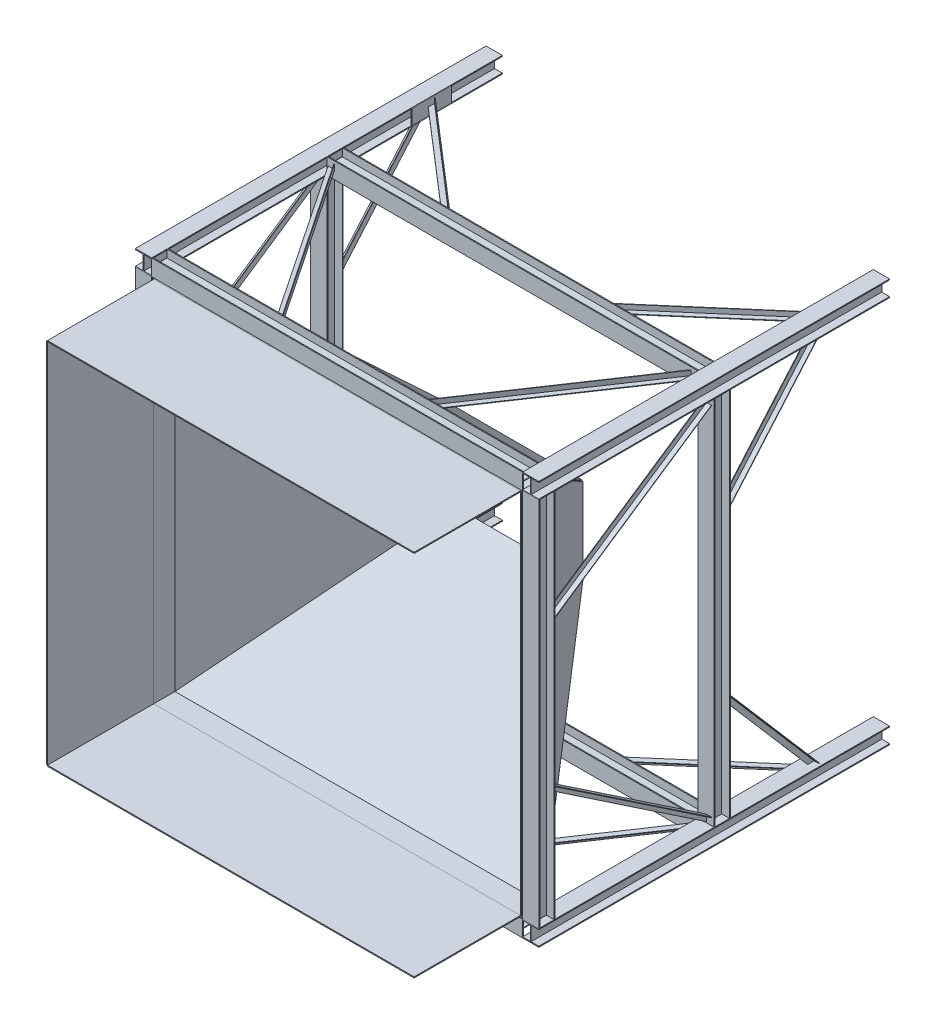
SolidWorks part; units mm, degrees
other "DetailItem1"
other "DetailItem2"
other "DetailItem3"
other "DetailItem4"
other "DetailItem5"
other "DetailItem6"
other "DetailItem7"
other "DetailItem8"
other "DetailItem9"
other "DetailItem10"
other "DetailItem11"
other "DetailItem12"
other "DetailItem13"
other "DetailItem14"
other "DetailItem15"
other "DetailItem16"
other "DetailItem17"
other "DetailItem18"
other "DetailItem19"
other "DetailItem20"
other "DetailItem21"
other "DetailItem22"
other "DetailItem23"
other "DetailItem24"
other "DetailItem25"
other "DetailItem26"
other "DetailItem27"
other "DetailItem28"
other "DetailItem29"
other "DetailItem30"
other "DetailItem31"
other "DetailItem32"
other "DetailItem33"
other "DetailItem34"
other "DetailItem35"
other "DetailItem36"
other "DetailItem37"
other "DetailItem38"
other "DetailItem39"
other "DetailItem40"
other "DetailItem41"
other "DetailItem42"
other "DetailItem43"
other "DetailItem44"
other "DetailItem45"
other "DetailItem46"
other "DetailItem47"
other "DetailItem48"
other "DetailItem49"
other "DetailItem50"
other "DetailItem51"
other "DetailItem52"
other "DetailItem53"
other "DetailItem54"
other "DetailItem55"
other "DetailItem56"
other "DetailItem57"
other "DetailItem58"
other "DetailItem59"
other "DetailItem60"
other "DetailItem61"
other "DetailItem62"
other "DetailItem63"
other "DetailItem64"
other "DetailItem65"
other "DetailItem66"
other "DetailItem67"
other "DetailItem68"
other "DetailItem69"
other "DetailItem70"
other "DetailItem71"
other "DetailItem72"
other "DetailItem73"
other "Carpeta de soldadura"
other "Cordón de soldadura1"
other "Soldadura Viga H carga 1650 B"
other "Soldadura Viga H carga 3300 A"
other "Soldadura Viga H carga 3300 B"
other "Soldadura asiento a tolva carga"
other "Soldadura asiento a bastidor carga"
other "Soldadura Viga H fondo 1650 A"
other "Soldadura Viga H fondo 1650 B"
other "Soldadura Viga H fondo 3300 A"
other "Soldadura Viga H fondo 3300 B"
other "Soldadura asiento a tolva fondo"
other "Soldadura asiento a bastidor fondo"
other "Soldadura Viga H izquierda 1650 A"
other "Soldadura Viga H izquierda 1650 B"
other "Soldadura Viga H izquierda 3300 A"
other "Soldadura Viga H izquierda 3300 B"
other "Soldadura asiento a tolva izquierda"
other "Soldadura asiento a bastidor izquierda"
other "Soldadura Viga H derecha 1650 A"
other "Soldadura Viga H derecha 1650 B"
other "Soldadura Viga H derecha 3300 A"
other "Soldadura Viga H derecha 3300 B"
other "Soldadura asiento a tolva derecha"
other "Soldadura asiento a bastidor derecha"
other "Soldadura Angular superior carga A inferior"
other "Soldadura Angular superior carga A superior"
other "Soldadura Angular inferior carga A inferior"
other "Soldadura Angular inferior carga A superior"
other "Soldadura Angular superior carga B inferior"
other "Soldadura Angular superior carga B superior"
other "Soldadura Angular inferior carga B inferior"
other "Soldadura Angular inferior carga B superior"
other "Soldadura Angular superior fondo A inferior"
other "Soldadura Angular superior fondo A superior"
other "Soldadura Angular inferior fondo A inferior"
other "Soldadura Angular inferior fondo A superior"
other "Soldadura Angular superior fondo B inferior"
other "Soldadura Angular superior fondo B superior"
other "Soldadura Angular inferior fondo B inferior"
other "Soldadura Angular inferior fondo B superior"
other "Soldadura Angular superior izquierda A inferior"
other "Soldadura Angular superior izquierda A superior"
other "Soldadura Angular inferior izquierda A inferior"
other "Soldadura Angular inferior izquierda A superior"
other "Soldadura Angular superior izquierda B inferior"
other "Soldadura Angular superior izquierda B superior"
other "Soldadura Angular inferior izquierda B inferior"
other "Soldadura Angular inferior izquierda B superior"
other "Soldadura Angular superior derecha A inferior"
other "Soldadura Angular superior derecha A superior"
other "Soldadura Angular inferior derecha A inferior"
other "Soldadura Angular inferior derecha A superior"
other "Soldadura Angular superior derecha B inferior"
other "Soldadura Angular superior derecha B superior"
other "Soldadura Angular inferior derecha B inferior"
other "Soldadura Angular inferior derecha B superior"
other "Soldadura alerón a collar lateral Y negativo"
other "Soldadura esquina del collar lateral Y negativo"
other "Soldadura quiebre del embudo lateral Y negativo"
other "Soldadura arista inclinada lateral Y negativo"
other "Soldadura esquina del collar carga"
other "Soldadura quiebre del embudo carga"
other "Soldadura arista inclinada carga"
other "Soldadura alerón a collar lateral Y positivo"
other "Soldadura esquina del collar lateral Y positivo"
other "Soldadura quiebre del embudo lateral Y positivo"
other "Soldadura arista inclinada lateral Y positivo"
other "Soldadura alerón a collar fondo X negativo"
other "Soldadura esquina del collar fondo X negativo"
other "Soldadura quiebre del embudo fondo X negativo"
other "Soldadura arista inclinada fondo X negativo"
other "Soldadura esquina alerones fondo Y positivo"
other "Soldadura esquina alerones fondo Y negativo"
material "ASTM A36 Steel"
ref_plane "Front Plane" through (0, 0, 0) normal (0, 0, 1) x (1, 0, 0)
ref_plane "Top Plane" through (0, 0, 0) normal (0, 1, 0) x (1, 0, 0)
ref_plane "Right Plane" through (0, 0, 0) normal (1, 0, 0) x (0, 0, -1)
sketch3d "Referencias 1"
  point P0 (0, 0, 0)
  point P1 (0, -190, 0)
  point P2 (200, 0, 0)
ref_plane "Plano de perfil 1 estructura" through (0, 0, 0) normal (0, 0, 1) x (1, 0, 0)
sketch "Contorno Columna H 1" plane through (0, 0, 0) normal (0, 0, 1) x (1, 0, 0)
  line L0 (-1898, -1898) -> (-1745, -1898)
  line L1 (-1745, -1898) -> (-1745, -1889)
  line L2 (-1745, -1889) -> (-1818.25, -1889)
  line L3 (-1818.25, -1889) -> (-1818.25, -1754)
  line L4 (-1818.25, -1754) -> (-1745, -1754)
  line L5 (-1745, -1754) -> (-1745, -1745)
  line L6 (-1745, -1745) -> (-1898, -1745)
  line L7 (-1898, -1745) -> (-1898, -1754)
  line L8 (-1898, -1754) -> (-1824.75, -1754)
  line L9 (-1824.75, -1754) -> (-1824.75, -1889)
  line L10 (-1824.75, -1889) -> (-1898, -1889)
  line L11 (-1898, -1889) -> (-1898, -1898)
extrude "Columna H 1" add sketch "Contorno Columna H 1" along normal blind 3300 separate body
sketch "Contorno Columna H 2" plane through (0, 0, 0) normal (0, 0, 1) x (1, 0, 0)
  line L0 (-1898, 1745) -> (-1745, 1745)
  line L1 (-1745, 1745) -> (-1745, 1754)
  line L2 (-1745, 1754) -> (-1818.25, 1754)
  line L3 (-1818.25, 1754) -> (-1818.25, 1889)
  line L4 (-1818.25, 1889) -> (-1745, 1889)
  line L5 (-1745, 1889) -> (-1745, 1898)
  line L6 (-1745, 1898) -> (-1898, 1898)
  line L7 (-1898, 1898) -> (-1898, 1889)
  line L8 (-1898, 1889) -> (-1824.75, 1889)
  line L9 (-1824.75, 1889) -> (-1824.75, 1754)
  line L10 (-1824.75, 1754) -> (-1898, 1754)
  line L11 (-1898, 1754) -> (-1898, 1745)
extrude "Columna H 2" add sketch "Contorno Columna H 2" along normal blind 3300 separate body
sketch "Contorno Columna H 3" plane through (0, 0, 0) normal (0, 0, 1) x (1, 0, 0)
  line L0 (1745, -1898) -> (1898, -1898)
  line L1 (1898, -1898) -> (1898, -1889)
  line L2 (1898, -1889) -> (1824.75, -1889)
  line L3 (1824.75, -1889) -> (1824.75, -1754)
  line L4 (1824.75, -1754) -> (1898, -1754)
  line L5 (1898, -1754) -> (1898, -1745)
  line L6 (1898, -1745) -> (1745, -1745)
  line L7 (1745, -1745) -> (1745, -1754)
  line L8 (1745, -1754) -> (1818.25, -1754)
  line L9 (1818.25, -1754) -> (1818.25, -1889)
  line L10 (1818.25, -1889) -> (1745, -1889)
  line L11 (1745, -1889) -> (1745, -1898)
extrude "Columna H 3" add sketch "Contorno Columna H 3" along normal blind 3300 separate body
sketch "Contorno Columna H 4" plane through (0, 0, 0) normal (0, 0, 1) x (1, 0, 0)
  line L0 (1745, 1745) -> (1898, 1745)
  line L1 (1898, 1745) -> (1898, 1754)
  line L2 (1898, 1754) -> (1824.75, 1754)
  line L3 (1824.75, 1754) -> (1824.75, 1889)
  line L4 (1824.75, 1889) -> (1898, 1889)
  line L5 (1898, 1889) -> (1898, 1898)
  line L6 (1898, 1898) -> (1745, 1898)
  line L7 (1745, 1898) -> (1745, 1889)
  line L8 (1745, 1889) -> (1818.25, 1889)
  line L9 (1818.25, 1889) -> (1818.25, 1754)
  line L10 (1818.25, 1754) -> (1745, 1754)
  line L11 (1745, 1754) -> (1745, 1745)
extrude "Columna H 4" add sketch "Contorno Columna H 4" along normal blind 3300 separate body
sketch3d "Referencias 2"
  point P0 (-1745, 0, 0)
  point P1 (-1745, 190, 0)
  point P2 (-1745, 0, 200)
ref_plane "Plano de perfil 2 estructura" through (-1745, 0, 0) normal (1, 0, 0) x (0, 0, -1)
sketch "Contorno Viga H carga 1650" plane through (-1745, 0, 0) normal (1, 0, 0) x (0, 0, -1)
  line L0 (-1497, -1745) -> (-1497, -1898)
  line L1 (-1497, -1898) -> (-1506, -1898)
  line L2 (-1506, -1898) -> (-1506, -1824.75)
  line L3 (-1506, -1824.75) -> (-1641, -1824.75)
  line L4 (-1641, -1824.75) -> (-1641, -1898)
  line L5 (-1641, -1898) -> (-1650, -1898)
  line L6 (-1650, -1898) -> (-1650, -1745)
  line L7 (-1650, -1745) -> (-1641, -1745)
  line L8 (-1641, -1745) -> (-1641, -1818.25)
  line L9 (-1641, -1818.25) -> (-1506, -1818.25)
  line L10 (-1506, -1818.25) -> (-1506, -1745)
  line L11 (-1506, -1745) -> (-1497, -1745)
extrude "Viga H carga 1650" add sketch "Contorno Viga H carga 1650" along normal blind 3490 separate body
sketch "Contorno Viga H carga 3300" plane through (-1745, 0, 0) normal (1, 0, 0) x (0, 0, -1)
  line L0 (-3147, -1745) -> (-3147, -1898)
  line L1 (-3147, -1898) -> (-3156, -1898)
  line L2 (-3156, -1898) -> (-3156, -1824.75)
  line L3 (-3156, -1824.75) -> (-3291, -1824.75)
  line L4 (-3291, -1824.75) -> (-3291, -1898)
  line L5 (-3291, -1898) -> (-3300, -1898)
  line L6 (-3300, -1898) -> (-3300, -1745)
  line L7 (-3300, -1745) -> (-3291, -1745)
  line L8 (-3291, -1745) -> (-3291, -1818.25)
  line L9 (-3291, -1818.25) -> (-3156, -1818.25)
  line L10 (-3156, -1818.25) -> (-3156, -1745)
  line L11 (-3156, -1745) -> (-3147, -1745)
extrude "Viga H carga 3300" add sketch "Contorno Viga H carga 3300" along normal blind 3490 separate body
sketch "Contorno Cierre columna carga A" plane through (-1745, 0, 0) normal (1, 0, 0) x (0, 0, -1)
  line L0 (-480, -1754) -> (-480, -1889)
  line L1 (-480, -1889) -> (-850, -1889)
  line L2 (-850, -1889) -> (-850, -1754)
  line L3 (-850, -1754) -> (-480, -1754)
extrude "Cierre columna carga A" add sketch "Contorno Cierre columna carga A" against normal blind 8 separate body
sketch3d "Referencias 3"
  point P0 (0, -1821.5, 0)
  point P1 (-190, -1821.5, 0)
  point P2 (0, -1821.5, 200)
ref_plane "Plano de perfil 3 estructura" through (0, -1821.5, 0) normal (0, 1, 0) x (1, 0, 0)
sketch "Contorno Ala plana Angular superior carga A" plane through (0, -1821.5, 0) normal (0, 1, 0) x (1, 0, 0)
  line L0 (-1674.8701, -1650) -> (-1735.1299, -1650)
  line L1 (-1735.1299, -1650) -> (-728.1299, -3147)
  line L2 (-728.1299, -3147) -> (-667.8701, -3147)
  line L3 (-667.8701, -3147) -> (-1674.8701, -1650)
extrude "Ala plana Angular superior carga A" add sketch "Contorno Ala plana Angular superior carga A" against normal blind 5 separate body
sketch3d "Referencias 4"
  point P0 (0, -1826.5, 0)
  point P1 (-190, -1826.5, 0)
  point P2 (0, -1826.5, 200)
ref_plane "Plano de perfil 4 estructura" through (0, -1826.5, 0) normal (0, 1, 0) x (1, 0, 0)
sketch "Contorno Retorno Angular superior carga A" plane through (0, -1826.5, 0) normal (0, 1, 0) x (1, 0, 0)
  line L0 (-1674.8701, -1650) -> (-1680.8961, -1650)
  line L1 (-1680.8961, -1650) -> (-673.8961, -3147)
  line L2 (-673.8961, -3147) -> (-667.8701, -3147)
  line L3 (-667.8701, -3147) -> (-1674.8701, -1650)
extrude "Retorno Angular superior carga A" add sketch "Contorno Retorno Angular superior carga A" against normal blind 45 separate body
combine bodies "Angular superior carga A" operation type add bodies to combine 108 109
sketch "Contorno Ala plana Angular inferior carga A" plane through (0, -1821.5, 0) normal (0, 1, 0) x (1, 0, 0)
  line L0 (-1745, -631.991) -> (-1745, -698.009)
  line L1 (-1745, -698.009) -> (-818.2856, -1497)
  line L2 (-818.2856, -1497) -> (-741.7144, -1497)
  line L3 (-741.7144, -1497) -> (-1745, -631.991)
extrude "Ala plana Angular inferior carga A" add sketch "Contorno Ala plana Angular inferior carga A" against normal blind 5 separate body
sketch "Contorno Retorno Angular inferior carga A" plane through (0, -1826.5, 0) normal (0, 1, 0) x (1, 0, 0)
  line L0 (-1745, -631.991) -> (-1745, -638.5928)
  line L1 (-1745, -638.5928) -> (-749.3715, -1497)
  line L2 (-749.3715, -1497) -> (-741.7144, -1497)
  line L3 (-741.7144, -1497) -> (-1745, -631.991)
extrude "Retorno Angular inferior carga A" add sketch "Contorno Retorno Angular inferior carga A" against normal blind 45 separate body
combine bodies "Angular inferior carga A" operation type add bodies to combine 111 112
sketch3d "Referencias 5"
  point P0 (1745, 0, 0)
  point P1 (1745, 190, 0)
  point P2 (1745, 0, 200)
ref_plane "Plano de perfil 5 estructura" through (1745, 0, 0) normal (1, 0, 0) x (0, 0, -1)
sketch "Contorno Cierre columna carga B" plane through (1745, 0, 0) normal (1, 0, 0) x (0, 0, -1)
  line L0 (-480, -1754) -> (-480, -1889)
  line L1 (-480, -1889) -> (-850, -1889)
  line L2 (-850, -1889) -> (-850, -1754)
  line L3 (-850, -1754) -> (-480, -1754)
extrude "Cierre columna carga B" add sketch "Contorno Cierre columna carga B" along normal blind 8 separate body
sketch "Contorno Ala plana Angular superior carga B" plane through (0, -1821.5, 0) normal (0, 1, 0) x (1, 0, 0)
  line L0 (1674.8701, -1650) -> (1735.1299, -1650)
  line L1 (1735.1299, -1650) -> (728.1299, -3147)
  line L2 (728.1299, -3147) -> (667.8701, -3147)
  line L3 (667.8701, -3147) -> (1674.8701, -1650)
extrude "Ala plana Angular superior carga B" add sketch "Contorno Ala plana Angular superior carga B" against normal blind 5 separate body
sketch "Contorno Retorno Angular superior carga B" plane through (0, -1826.5, 0) normal (0, 1, 0) x (1, 0, 0)
  line L0 (1674.8701, -1650) -> (1680.8961, -1650)
  line L1 (1680.8961, -1650) -> (673.8961, -3147)
  line L2 (673.8961, -3147) -> (667.8701, -3147)
  line L3 (667.8701, -3147) -> (1674.8701, -1650)
extrude "Retorno Angular superior carga B" add sketch "Contorno Retorno Angular superior carga B" against normal blind 45 separate body
combine bodies "Angular superior carga B" operation type add bodies to combine 115 116
sketch "Contorno Ala plana Angular inferior carga B" plane through (0, -1821.5, 0) normal (0, 1, 0) x (1, 0, 0)
  line L0 (1745, -631.991) -> (1745, -698.009)
  line L1 (1745, -698.009) -> (818.2856, -1497)
  line L2 (818.2856, -1497) -> (741.7144, -1497)
  line L3 (741.7144, -1497) -> (1745, -631.991)
extrude "Ala plana Angular inferior carga B" add sketch "Contorno Ala plana Angular inferior carga B" against normal blind 5 separate body
sketch "Contorno Retorno Angular inferior carga B" plane through (0, -1826.5, 0) normal (0, 1, 0) x (1, 0, 0)
  line L0 (1745, -631.991) -> (1745, -638.5928)
  line L1 (1745, -638.5928) -> (749.3715, -1497)
  line L2 (749.3715, -1497) -> (741.7144, -1497)
  line L3 (741.7144, -1497) -> (1745, -631.991)
extrude "Retorno Angular inferior carga B" add sketch "Contorno Retorno Angular inferior carga B" against normal blind 45 separate body
combine bodies "Angular inferior carga B" operation type add bodies to combine 118 119
sketch3d "Referencias 6"
  point P0 (0, 0, 3281.475)
  point P1 (0, -190, 3281.475)
  point P2 (200, 0, 3281.475)
ref_plane "Plano de perfil 6 estructura" through (0, 0, 3281.475) normal (0, 0, 1) x (1, 0, 0)
sketch "Contorno Asiento soldado carga" plane through (0, 0, 3281.475) normal (0, 0, 1) x (1, 0, 0)
  line L0 (-1450, -1734.525) -> (1450, -1734.525)
  line L1 (1450, -1734.525) -> (1450, -1818.25)
  line L2 (1450, -1818.25) -> (-1450, -1818.25)
  line L3 (-1450, -1818.25) -> (-1450, -1734.525)
extrude "Asiento soldado carga" add sketch "Contorno Asiento soldado carga" along normal blind 9.525 separate body
sketch "Contorno Viga H fondo 1650" plane through (-1745, 0, 0) normal (1, 0, 0) x (0, 0, -1)
  line L0 (-1497, 1745) -> (-1497, 1898)
  line L1 (-1497, 1898) -> (-1506, 1898)
  line L2 (-1506, 1898) -> (-1506, 1824.75)
  line L3 (-1506, 1824.75) -> (-1641, 1824.75)
  line L4 (-1641, 1824.75) -> (-1641, 1898)
  line L5 (-1641, 1898) -> (-1650, 1898)
  line L6 (-1650, 1898) -> (-1650, 1745)
  line L7 (-1650, 1745) -> (-1641, 1745)
  line L8 (-1641, 1745) -> (-1641, 1818.25)
  line L9 (-1641, 1818.25) -> (-1506, 1818.25)
  line L10 (-1506, 1818.25) -> (-1506, 1745)
  line L11 (-1506, 1745) -> (-1497, 1745)
extrude "Viga H fondo 1650" add sketch "Contorno Viga H fondo 1650" along normal blind 3490 separate body
sketch "Contorno Viga H fondo 3300" plane through (-1745, 0, 0) normal (1, 0, 0) x (0, 0, -1)
  line L0 (-3147, 1745) -> (-3147, 1898)
  line L1 (-3147, 1898) -> (-3156, 1898)
  line L2 (-3156, 1898) -> (-3156, 1824.75)
  line L3 (-3156, 1824.75) -> (-3291, 1824.75)
  line L4 (-3291, 1824.75) -> (-3291, 1898)
  line L5 (-3291, 1898) -> (-3300, 1898)
  line L6 (-3300, 1898) -> (-3300, 1745)
  line L7 (-3300, 1745) -> (-3291, 1745)
  line L8 (-3291, 1745) -> (-3291, 1818.25)
  line L9 (-3291, 1818.25) -> (-3156, 1818.25)
  line L10 (-3156, 1818.25) -> (-3156, 1745)
  line L11 (-3156, 1745) -> (-3147, 1745)
extrude "Viga H fondo 3300" add sketch "Contorno Viga H fondo 3300" along normal blind 3490 separate body
sketch "Contorno Cierre columna fondo A" plane through (-1745, 0, 0) normal (1, 0, 0) x (0, 0, -1)
  line L0 (-480, 1754) -> (-480, 1889)
  line L1 (-480, 1889) -> (-850, 1889)
  line L2 (-850, 1889) -> (-850, 1754)
  line L3 (-850, 1754) -> (-480, 1754)
extrude "Cierre columna fondo A" add sketch "Contorno Cierre columna fondo A" against normal blind 8 separate body
sketch3d "Referencias 7"
  point P0 (0, 1821.5, 0)
  point P1 (-190, 1821.5, 0)
  point P2 (0, 1821.5, 200)
ref_plane "Plano de perfil 7 estructura" through (0, 1821.5, 0) normal (0, 1, 0) x (1, 0, 0)
sketch "Contorno Ala plana Angular superior fondo A" plane through (0, 1821.5, 0) normal (0, 1, 0) x (1, 0, 0)
  line L0 (-1674.8701, -1650) -> (-1735.1299, -1650)
  line L1 (-1735.1299, -1650) -> (-728.1299, -3147)
  line L2 (-728.1299, -3147) -> (-667.8701, -3147)
  line L3 (-667.8701, -3147) -> (-1674.8701, -1650)
extrude "Ala plana Angular superior fondo A" add sketch "Contorno Ala plana Angular superior fondo A" along normal blind 5 separate body
sketch3d "Referencias 8"
  point P0 (0, 1826.5, 0)
  point P1 (-190, 1826.5, 0)
  point P2 (0, 1826.5, 200)
ref_plane "Plano de perfil 8 estructura" through (0, 1826.5, 0) normal (0, 1, 0) x (1, 0, 0)
sketch "Contorno Retorno Angular superior fondo A" plane through (0, 1826.5, 0) normal (0, 1, 0) x (1, 0, 0)
  line L0 (-1674.8701, -1650) -> (-1680.8961, -1650)
  line L1 (-1680.8961, -1650) -> (-673.8961, -3147)
  line L2 (-673.8961, -3147) -> (-667.8701, -3147)
  line L3 (-667.8701, -3147) -> (-1674.8701, -1650)
extrude "Retorno Angular superior fondo A" add sketch "Contorno Retorno Angular superior fondo A" along normal blind 45 separate body
combine bodies "Angular superior fondo A" operation type add bodies to combine 125 126
sketch "Contorno Ala plana Angular inferior fondo A" plane through (0, 1821.5, 0) normal (0, 1, 0) x (1, 0, 0)
  line L0 (-1745, -631.991) -> (-1745, -698.009)
  line L1 (-1745, -698.009) -> (-818.2856, -1497)
  line L2 (-818.2856, -1497) -> (-741.7144, -1497)
  line L3 (-741.7144, -1497) -> (-1745, -631.991)
extrude "Ala plana Angular inferior fondo A" add sketch "Contorno Ala plana Angular inferior fondo A" along normal blind 5 separate body
sketch "Contorno Retorno Angular inferior fondo A" plane through (0, 1826.5, 0) normal (0, 1, 0) x (1, 0, 0)
  line L0 (-1745, -631.991) -> (-1745, -638.5928)
  line L1 (-1745, -638.5928) -> (-749.3715, -1497)
  line L2 (-749.3715, -1497) -> (-741.7144, -1497)
  line L3 (-741.7144, -1497) -> (-1745, -631.991)
extrude "Retorno Angular inferior fondo A" add sketch "Contorno Retorno Angular inferior fondo A" along normal blind 45 separate body
combine bodies "Angular inferior fondo A" operation type add bodies to combine 128 129
sketch "Contorno Cierre columna fondo B" plane through (1745, 0, 0) normal (1, 0, 0) x (0, 0, -1)
  line L0 (-480, 1754) -> (-480, 1889)
  line L1 (-480, 1889) -> (-850, 1889)
  line L2 (-850, 1889) -> (-850, 1754)
  line L3 (-850, 1754) -> (-480, 1754)
extrude "Cierre columna fondo B" add sketch "Contorno Cierre columna fondo B" along normal blind 8 separate body
sketch "Contorno Ala plana Angular superior fondo B" plane through (0, 1821.5, 0) normal (0, 1, 0) x (1, 0, 0)
  line L0 (1674.8701, -1650) -> (1735.1299, -1650)
  line L1 (1735.1299, -1650) -> (728.1299, -3147)
  line L2 (728.1299, -3147) -> (667.8701, -3147)
  line L3 (667.8701, -3147) -> (1674.8701, -1650)
extrude "Ala plana Angular superior fondo B" add sketch "Contorno Ala plana Angular superior fondo B" along normal blind 5 separate body
sketch "Contorno Retorno Angular superior fondo B" plane through (0, 1826.5, 0) normal (0, 1, 0) x (1, 0, 0)
  line L0 (1674.8701, -1650) -> (1680.8961, -1650)
  line L1 (1680.8961, -1650) -> (673.8961, -3147)
  line L2 (673.8961, -3147) -> (667.8701, -3147)
  line L3 (667.8701, -3147) -> (1674.8701, -1650)
extrude "Retorno Angular superior fondo B" add sketch "Contorno Retorno Angular superior fondo B" along normal blind 45 separate body
combine bodies "Angular superior fondo B" operation type add bodies to combine 132 133
sketch "Contorno Ala plana Angular inferior fondo B" plane through (0, 1821.5, 0) normal (0, 1, 0) x (1, 0, 0)
  line L0 (1745, -631.991) -> (1745, -698.009)
  line L1 (1745, -698.009) -> (818.2856, -1497)
  line L2 (818.2856, -1497) -> (741.7144, -1497)
  line L3 (741.7144, -1497) -> (1745, -631.991)
extrude "Ala plana Angular inferior fondo B" add sketch "Contorno Ala plana Angular inferior fondo B" along normal blind 5 separate body
sketch "Contorno Retorno Angular inferior fondo B" plane through (0, 1826.5, 0) normal (0, 1, 0) x (1, 0, 0)
  line L0 (1745, -631.991) -> (1745, -638.5928)
  line L1 (1745, -638.5928) -> (749.3715, -1497)
  line L2 (749.3715, -1497) -> (741.7144, -1497)
  line L3 (741.7144, -1497) -> (1745, -631.991)
extrude "Retorno Angular inferior fondo B" add sketch "Contorno Retorno Angular inferior fondo B" along normal blind 45 separate body
combine bodies "Angular inferior fondo B" operation type add bodies to combine 135 136
sketch "Contorno Asiento soldado fondo" plane through (0, 0, 3281.475) normal (0, 0, 1) x (1, 0, 0)
  line L0 (-1450, 1734.525) -> (1450, 1734.525)
  line L1 (1450, 1734.525) -> (1450, 1818.25)
  line L2 (1450, 1818.25) -> (-1450, 1818.25)
  line L3 (-1450, 1818.25) -> (-1450, 1734.525)
extrude "Asiento soldado fondo" add sketch "Contorno Asiento soldado fondo" along normal blind 9.525 separate body
sketch3d "Referencias 9"
  point P0 (0, -1745, 0)
  point P1 (-190, -1745, 0)
  point P2 (0, -1745, 200)
ref_plane "Plano de perfil 9 estructura" through (0, -1745, 0) normal (0, 1, 0) x (1, 0, 0)
sketch "Contorno Viga H izquierda 1650" plane through (0, -1745, 0) normal (0, 1, 0) x (1, 0, 0)
  line L0 (-1745, -1497) -> (-1898, -1497)
  line L1 (-1898, -1497) -> (-1898, -1506)
  line L2 (-1898, -1506) -> (-1824.75, -1506)
  line L3 (-1824.75, -1506) -> (-1824.75, -1641)
  line L4 (-1824.75, -1641) -> (-1898, -1641)
  line L5 (-1898, -1641) -> (-1898, -1650)
  line L6 (-1898, -1650) -> (-1745, -1650)
  line L7 (-1745, -1650) -> (-1745, -1641)
  line L8 (-1745, -1641) -> (-1818.25, -1641)
  line L9 (-1818.25, -1641) -> (-1818.25, -1506)
  line L10 (-1818.25, -1506) -> (-1745, -1506)
  line L11 (-1745, -1506) -> (-1745, -1497)
extrude "Viga H izquierda 1650" add sketch "Contorno Viga H izquierda 1650" along normal blind 3490 separate body
sketch "Contorno Viga H izquierda 3300" plane through (0, -1745, 0) normal (0, 1, 0) x (1, 0, 0)
  line L0 (-1745, -3147) -> (-1898, -3147)
  line L1 (-1898, -3147) -> (-1898, -3156)
  line L2 (-1898, -3156) -> (-1824.75, -3156)
  line L3 (-1824.75, -3156) -> (-1824.75, -3291)
  line L4 (-1824.75, -3291) -> (-1898, -3291)
  line L5 (-1898, -3291) -> (-1898, -3300)
  line L6 (-1898, -3300) -> (-1745, -3300)
  line L7 (-1745, -3300) -> (-1745, -3291)
  line L8 (-1745, -3291) -> (-1818.25, -3291)
  line L9 (-1818.25, -3291) -> (-1818.25, -3156)
  line L10 (-1818.25, -3156) -> (-1745, -3156)
  line L11 (-1745, -3156) -> (-1745, -3147)
extrude "Viga H izquierda 3300" add sketch "Contorno Viga H izquierda 3300" along normal blind 3490 separate body
sketch3d "Referencias 10"
  point P0 (-1821.5, 0, 0)
  point P1 (-1821.5, 190, 0)
  point P2 (-1821.5, 0, 200)
ref_plane "Plano de perfil 10 estructura" through (-1821.5, 0, 0) normal (1, 0, 0) x (0, 0, -1)
sketch "Contorno Ala plana Angular superior izquierda A" plane through (-1821.5, 0, 0) normal (1, 0, 0) x (0, 0, -1)
  line L0 (-1650, -1674.8701) -> (-1650, -1735.1299)
  line L1 (-1650, -1735.1299) -> (-3147, -728.1299)
  line L2 (-3147, -728.1299) -> (-3147, -667.8701)
  line L3 (-3147, -667.8701) -> (-1650, -1674.8701)
extrude "Ala plana Angular superior izquierda A" add sketch "Contorno Ala plana Angular superior izquierda A" against normal blind 5 separate body
sketch3d "Referencias 11"
  point P0 (-1826.5, 0, 0)
  point P1 (-1826.5, 190, 0)
  point P2 (-1826.5, 0, 200)
ref_plane "Plano de perfil 11 estructura" through (-1826.5, 0, 0) normal (1, 0, 0) x (0, 0, -1)
sketch "Contorno Retorno Angular superior izquierda A" plane through (-1826.5, 0, 0) normal (1, 0, 0) x (0, 0, -1)
  line L0 (-1650, -1674.8701) -> (-1650, -1680.8961)
  line L1 (-1650, -1680.8961) -> (-3147, -673.8961)
  line L2 (-3147, -673.8961) -> (-3147, -667.8701)
  line L3 (-3147, -667.8701) -> (-1650, -1674.8701)
extrude "Retorno Angular superior izquierda A" add sketch "Contorno Retorno Angular superior izquierda A" against normal blind 45 separate body
combine bodies "Angular superior izquierda A" operation type add bodies to combine 141 142
sketch "Contorno Ala plana Angular inferior izquierda A" plane through (-1821.5, 0, 0) normal (1, 0, 0) x (0, 0, -1)
  line L0 (-631.991, -1745) -> (-698.009, -1745)
  line L1 (-698.009, -1745) -> (-1497, -818.2856)
  line L2 (-1497, -818.2856) -> (-1497, -741.7144)
  line L3 (-1497, -741.7144) -> (-631.991, -1745)
extrude "Ala plana Angular inferior izquierda A" add sketch "Contorno Ala plana Angular inferior izquierda A" against normal blind 5 separate body
sketch "Contorno Retorno Angular inferior izquierda A" plane through (-1826.5, 0, 0) normal (1, 0, 0) x (0, 0, -1)
  line L0 (-631.991, -1745) -> (-638.5928, -1745)
  line L1 (-638.5928, -1745) -> (-1497, -749.3715)
  line L2 (-1497, -749.3715) -> (-1497, -741.7144)
  line L3 (-1497, -741.7144) -> (-631.991, -1745)
extrude "Retorno Angular inferior izquierda A" add sketch "Contorno Retorno Angular inferior izquierda A" against normal blind 45 separate body
combine bodies "Angular inferior izquierda A" operation type add bodies to combine 144 145
sketch "Contorno Ala plana Angular superior izquierda B" plane through (-1821.5, 0, 0) normal (1, 0, 0) x (0, 0, -1)
  line L0 (-1650, 1674.8701) -> (-1650, 1735.1299)
  line L1 (-1650, 1735.1299) -> (-3147, 728.1299)
  line L2 (-3147, 728.1299) -> (-3147, 667.8701)
  line L3 (-3147, 667.8701) -> (-1650, 1674.8701)
extrude "Ala plana Angular superior izquierda B" add sketch "Contorno Ala plana Angular superior izquierda B" against normal blind 5 separate body
sketch "Contorno Retorno Angular superior izquierda B" plane through (-1826.5, 0, 0) normal (1, 0, 0) x (0, 0, -1)
  line L0 (-1650, 1674.8701) -> (-1650, 1680.8961)
  line L1 (-1650, 1680.8961) -> (-3147, 673.8961)
  line L2 (-3147, 673.8961) -> (-3147, 667.8701)
  line L3 (-3147, 667.8701) -> (-1650, 1674.8701)
extrude "Retorno Angular superior izquierda B" add sketch "Contorno Retorno Angular superior izquierda B" against normal blind 45 separate body
combine bodies "Angular superior izquierda B" operation type add bodies to combine 147 148
sketch "Contorno Ala plana Angular inferior izquierda B" plane through (-1821.5, 0, 0) normal (1, 0, 0) x (0, 0, -1)
  line L0 (-631.991, 1745) -> (-698.009, 1745)
  line L1 (-698.009, 1745) -> (-1497, 818.2856)
  line L2 (-1497, 818.2856) -> (-1497, 741.7144)
  line L3 (-1497, 741.7144) -> (-631.991, 1745)
extrude "Ala plana Angular inferior izquierda B" add sketch "Contorno Ala plana Angular inferior izquierda B" against normal blind 5 separate body
sketch "Contorno Retorno Angular inferior izquierda B" plane through (-1826.5, 0, 0) normal (1, 0, 0) x (0, 0, -1)
  line L0 (-631.991, 1745) -> (-638.5928, 1745)
  line L1 (-638.5928, 1745) -> (-1497, 749.3715)
  line L2 (-1497, 749.3715) -> (-1497, 741.7144)
  line L3 (-1497, 741.7144) -> (-631.991, 1745)
extrude "Retorno Angular inferior izquierda B" add sketch "Contorno Retorno Angular inferior izquierda B" against normal blind 45 separate body
combine bodies "Angular inferior izquierda B" operation type add bodies to combine 150 151
sketch "Contorno Asiento soldado izquierda" plane through (0, 0, 3281.475) normal (0, 0, 1) x (1, 0, 0)
  line L0 (-1734.525, -1450) -> (-1734.525, 1450)
  line L1 (-1734.525, 1450) -> (-1818.25, 1450)
  line L2 (-1818.25, 1450) -> (-1818.25, -1450)
  line L3 (-1818.25, -1450) -> (-1734.525, -1450)
extrude "Asiento soldado izquierda" add sketch "Contorno Asiento soldado izquierda" along normal blind 9.525 separate body
sketch "Contorno Viga H derecha 1650" plane through (0, -1745, 0) normal (0, 1, 0) x (1, 0, 0)
  line L0 (1745, -1497) -> (1898, -1497)
  line L1 (1898, -1497) -> (1898, -1506)
  line L2 (1898, -1506) -> (1824.75, -1506)
  line L3 (1824.75, -1506) -> (1824.75, -1641)
  line L4 (1824.75, -1641) -> (1898, -1641)
  line L5 (1898, -1641) -> (1898, -1650)
  line L6 (1898, -1650) -> (1745, -1650)
  line L7 (1745, -1650) -> (1745, -1641)
  line L8 (1745, -1641) -> (1818.25, -1641)
  line L9 (1818.25, -1641) -> (1818.25, -1506)
  line L10 (1818.25, -1506) -> (1745, -1506)
  line L11 (1745, -1506) -> (1745, -1497)
extrude "Viga H derecha 1650" add sketch "Contorno Viga H derecha 1650" along normal blind 3490 separate body
sketch "Contorno Viga H derecha 3300" plane through (0, -1745, 0) normal (0, 1, 0) x (1, 0, 0)
  line L0 (1745, -3147) -> (1898, -3147)
  line L1 (1898, -3147) -> (1898, -3156)
  line L2 (1898, -3156) -> (1824.75, -3156)
  line L3 (1824.75, -3156) -> (1824.75, -3291)
  line L4 (1824.75, -3291) -> (1898, -3291)
  line L5 (1898, -3291) -> (1898, -3300)
  line L6 (1898, -3300) -> (1745, -3300)
  line L7 (1745, -3300) -> (1745, -3291)
  line L8 (1745, -3291) -> (1818.25, -3291)
  line L9 (1818.25, -3291) -> (1818.25, -3156)
  line L10 (1818.25, -3156) -> (1745, -3156)
  line L11 (1745, -3156) -> (1745, -3147)
extrude "Viga H derecha 3300" add sketch "Contorno Viga H derecha 3300" along normal blind 3490 separate body
sketch3d "Referencias 12"
  point P0 (1821.5, 0, 0)
  point P1 (1821.5, 190, 0)
  point P2 (1821.5, 0, 200)
ref_plane "Plano de perfil 12 estructura" through (1821.5, 0, 0) normal (1, 0, 0) x (0, 0, -1)
sketch "Contorno Ala plana Angular superior derecha A" plane through (1821.5, 0, 0) normal (1, 0, 0) x (0, 0, -1)
  line L0 (-1650, -1674.8701) -> (-1650, -1735.1299)
  line L1 (-1650, -1735.1299) -> (-3147, -728.1299)
  line L2 (-3147, -728.1299) -> (-3147, -667.8701)
  line L3 (-3147, -667.8701) -> (-1650, -1674.8701)
extrude "Ala plana Angular superior derecha A" add sketch "Contorno Ala plana Angular superior derecha A" along normal blind 5 separate body
sketch3d "Referencias 13"
  point P0 (1826.5, 0, 0)
  point P1 (1826.5, 190, 0)
  point P2 (1826.5, 0, 200)
ref_plane "Plano de perfil 13 estructura" through (1826.5, 0, 0) normal (1, 0, 0) x (0, 0, -1)
sketch "Contorno Retorno Angular superior derecha A" plane through (1826.5, 0, 0) normal (1, 0, 0) x (0, 0, -1)
  line L0 (-1650, -1674.8701) -> (-1650, -1680.8961)
  line L1 (-1650, -1680.8961) -> (-3147, -673.8961)
  line L2 (-3147, -673.8961) -> (-3147, -667.8701)
  line L3 (-3147, -667.8701) -> (-1650, -1674.8701)
extrude "Retorno Angular superior derecha A" add sketch "Contorno Retorno Angular superior derecha A" along normal blind 45 separate body
combine bodies "Angular superior derecha A" operation type add bodies to combine 156 157
sketch "Contorno Ala plana Angular inferior derecha A" plane through (1821.5, 0, 0) normal (1, 0, 0) x (0, 0, -1)
  line L0 (-631.991, -1745) -> (-698.009, -1745)
  line L1 (-698.009, -1745) -> (-1497, -818.2856)
  line L2 (-1497, -818.2856) -> (-1497, -741.7144)
  line L3 (-1497, -741.7144) -> (-631.991, -1745)
extrude "Ala plana Angular inferior derecha A" add sketch "Contorno Ala plana Angular inferior derecha A" along normal blind 5 separate body
sketch "Contorno Retorno Angular inferior derecha A" plane through (1826.5, 0, 0) normal (1, 0, 0) x (0, 0, -1)
  line L0 (-631.991, -1745) -> (-638.5928, -1745)
  line L1 (-638.5928, -1745) -> (-1497, -749.3715)
  line L2 (-1497, -749.3715) -> (-1497, -741.7144)
  line L3 (-1497, -741.7144) -> (-631.991, -1745)
extrude "Retorno Angular inferior derecha A" add sketch "Contorno Retorno Angular inferior derecha A" along normal blind 45 separate body
combine bodies "Angular inferior derecha A" operation type add bodies to combine 159 160
sketch "Contorno Ala plana Angular superior derecha B" plane through (1821.5, 0, 0) normal (1, 0, 0) x (0, 0, -1)
  line L0 (-1650, 1674.8701) -> (-1650, 1735.1299)
  line L1 (-1650, 1735.1299) -> (-3147, 728.1299)
  line L2 (-3147, 728.1299) -> (-3147, 667.8701)
  line L3 (-3147, 667.8701) -> (-1650, 1674.8701)
extrude "Ala plana Angular superior derecha B" add sketch "Contorno Ala plana Angular superior derecha B" along normal blind 5 separate body
sketch "Contorno Retorno Angular superior derecha B" plane through (1826.5, 0, 0) normal (1, 0, 0) x (0, 0, -1)
  line L0 (-1650, 1674.8701) -> (-1650, 1680.8961)
  line L1 (-1650, 1680.8961) -> (-3147, 673.8961)
  line L2 (-3147, 673.8961) -> (-3147, 667.8701)
  line L3 (-3147, 667.8701) -> (-1650, 1674.8701)
extrude "Retorno Angular superior derecha B" add sketch "Contorno Retorno Angular superior derecha B" along normal blind 45 separate body
combine bodies "Angular superior derecha B" operation type add bodies to combine 162 163
sketch "Contorno Ala plana Angular inferior derecha B" plane through (1821.5, 0, 0) normal (1, 0, 0) x (0, 0, -1)
  line L0 (-631.991, 1745) -> (-698.009, 1745)
  line L1 (-698.009, 1745) -> (-1497, 818.2856)
  line L2 (-1497, 818.2856) -> (-1497, 741.7144)
  line L3 (-1497, 741.7144) -> (-631.991, 1745)
extrude "Ala plana Angular inferior derecha B" add sketch "Contorno Ala plana Angular inferior derecha B" along normal blind 5 separate body
sketch "Contorno Retorno Angular inferior derecha B" plane through (1826.5, 0, 0) normal (1, 0, 0) x (0, 0, -1)
  line L0 (-631.991, 1745) -> (-638.5928, 1745)
  line L1 (-638.5928, 1745) -> (-1497, 749.3715)
  line L2 (-1497, 749.3715) -> (-1497, 741.7144)
  line L3 (-1497, 741.7144) -> (-631.991, 1745)
extrude "Retorno Angular inferior derecha B" add sketch "Contorno Retorno Angular inferior derecha B" along normal blind 45 separate body
combine bodies "Angular inferior derecha B" operation type add bodies to combine 165 166
sketch "Contorno Asiento soldado derecha" plane through (0, 0, 3281.475) normal (0, 0, 1) x (1, 0, 0)
  line L0 (1734.525, -1450) -> (1734.525, 1450)
  line L1 (1734.525, 1450) -> (1818.25, 1450)
  line L2 (1818.25, 1450) -> (1818.25, -1450)
  line L3 (1818.25, -1450) -> (1734.525, -1450)
extrude "Asiento soldado derecha" add sketch "Contorno Asiento soldado derecha" along normal blind 9.525 separate body
sketch3d "Junta Viga H carga 1650 A"
  line L0 (-1745, -1745, 1650) -> (-1745, -1898, 1650)
sketch3d "Junta Viga H carga 1650 B"
  line L0 (1745, -1745, 1650) -> (1745, -1898, 1650)
sketch3d "Junta Viga H carga 3300 A"
  line L0 (-1745, -1745, 3300) -> (-1745, -1898, 3300)
sketch3d "Junta Viga H carga 3300 B"
  line L0 (1745, -1745, 3300) -> (1745, -1898, 3300)
sketch3d "Junta Angular superior carga A inferior"
  line L0 (-1674.8701, -1821.5, 1650) -> (-1735.1299, -1821.5, 1650)
sketch3d "Junta Angular superior carga A superior"
  line L0 (-667.8701, -1821.5, 3147) -> (-728.1299, -1821.5, 3147)
sketch3d "Junta Angular inferior carga A inferior"
  line L0 (-1745, -1821.5, 631.991) -> (-1745, -1821.5, 698.009)
sketch3d "Junta Angular inferior carga A superior"
  line L0 (-741.7144, -1821.5, 1497) -> (-818.2856, -1821.5, 1497)
sketch3d "Junta Angular superior carga B inferior"
  line L0 (1674.8701, -1821.5, 1650) -> (1735.1299, -1821.5, 1650)
sketch3d "Junta Angular superior carga B superior"
  line L0 (667.8701, -1821.5, 3147) -> (728.1299, -1821.5, 3147)
sketch3d "Junta Angular inferior carga B inferior"
  line L0 (1745, -1821.5, 631.991) -> (1745, -1821.5, 698.009)
sketch3d "Junta Angular inferior carga B superior"
  line L0 (741.7144, -1821.5, 1497) -> (818.2856, -1821.5, 1497)
sketch3d "Junta asiento a tolva carga"
  line L0 (-1450, -1734.525, 3281.475) -> (1450, -1734.525, 3281.475)
sketch3d "Junta asiento a bastidor carga"
  line L0 (-1450, -1745, 3291) -> (1450, -1745, 3291)
sketch3d "Junta Viga H fondo 1650 A"
  line L0 (-1745, 1745, 1650) -> (-1745, 1898, 1650)
sketch3d "Junta Viga H fondo 1650 B"
  line L0 (1745, 1745, 1650) -> (1745, 1898, 1650)
sketch3d "Junta Viga H fondo 3300 A"
  line L0 (-1745, 1745, 3300) -> (-1745, 1898, 3300)
sketch3d "Junta Viga H fondo 3300 B"
  line L0 (1745, 1745, 3300) -> (1745, 1898, 3300)
sketch3d "Junta Angular superior fondo A inferior"
  line L0 (-1674.8701, 1821.5, 1650) -> (-1735.1299, 1821.5, 1650)
sketch3d "Junta Angular superior fondo A superior"
  line L0 (-667.8701, 1821.5, 3147) -> (-728.1299, 1821.5, 3147)
sketch3d "Junta Angular inferior fondo A inferior"
  line L0 (-1745, 1821.5, 631.991) -> (-1745, 1821.5, 698.009)
sketch3d "Junta Angular inferior fondo A superior"
  line L0 (-741.7144, 1821.5, 1497) -> (-818.2856, 1821.5, 1497)
sketch3d "Junta Angular superior fondo B inferior"
  line L0 (1674.8701, 1821.5, 1650) -> (1735.1299, 1821.5, 1650)
sketch3d "Junta Angular superior fondo B superior"
  line L0 (667.8701, 1821.5, 3147) -> (728.1299, 1821.5, 3147)
sketch3d "Junta Angular inferior fondo B inferior"
  line L0 (1745, 1821.5, 631.991) -> (1745, 1821.5, 698.009)
sketch3d "Junta Angular inferior fondo B superior"
  line L0 (741.7144, 1821.5, 1497) -> (818.2856, 1821.5, 1497)
sketch3d "Junta asiento a tolva fondo"
  line L0 (-1450, 1734.525, 3281.475) -> (1450, 1734.525, 3281.475)
sketch3d "Junta asiento a bastidor fondo"
  line L0 (-1450, 1745, 3291) -> (1450, 1745, 3291)
sketch3d "Junta Viga H izquierda 1650 A"
  line L0 (-1745, -1745, 1650) -> (-1898, -1745, 1650)
sketch3d "Junta Viga H izquierda 1650 B"
  line L0 (-1745, 1745, 1650) -> (-1898, 1745, 1650)
sketch3d "Junta Viga H izquierda 3300 A"
  line L0 (-1745, -1745, 3300) -> (-1898, -1745, 3300)
sketch3d "Junta Viga H izquierda 3300 B"
  line L0 (-1745, 1745, 3300) -> (-1898, 1745, 3300)
sketch3d "Junta Angular superior izquierda A inferior"
  line L0 (-1821.5, -1674.8701, 1650) -> (-1821.5, -1735.1299, 1650)
sketch3d "Junta Angular superior izquierda A superior"
  line L0 (-1821.5, -667.8701, 3147) -> (-1821.5, -728.1299, 3147)
sketch3d "Junta Angular inferior izquierda A inferior"
  line L0 (-1821.5, -1745, 631.991) -> (-1821.5, -1745, 698.009)
sketch3d "Junta Angular inferior izquierda A superior"
  line L0 (-1821.5, -741.7144, 1497) -> (-1821.5, -818.2856, 1497)
sketch3d "Junta Angular superior izquierda B inferior"
  line L0 (-1821.5, 1674.8701, 1650) -> (-1821.5, 1735.1299, 1650)
sketch3d "Junta Angular superior izquierda B superior"
  line L0 (-1821.5, 667.8701, 3147) -> (-1821.5, 728.1299, 3147)
sketch3d "Junta Angular inferior izquierda B inferior"
  line L0 (-1821.5, 1745, 631.991) -> (-1821.5, 1745, 698.009)
sketch3d "Junta Angular inferior izquierda B superior"
  line L0 (-1821.5, 741.7144, 1497) -> (-1821.5, 818.2856, 1497)
sketch3d "Junta asiento a tolva izquierda"
  line L0 (-1734.525, -1450, 3281.475) -> (-1734.525, 1450, 3281.475)
sketch3d "Junta asiento a bastidor izquierda"
  line L0 (-1745, -1450, 3291) -> (-1745, 1450, 3291)
sketch3d "Junta Viga H derecha 1650 A"
  line L0 (1745, -1745, 1650) -> (1898, -1745, 1650)
sketch3d "Junta Viga H derecha 1650 B"
  line L0 (1745, 1745, 1650) -> (1898, 1745, 1650)
sketch3d "Junta Viga H derecha 3300 A"
  line L0 (1745, -1745, 3300) -> (1898, -1745, 3300)
sketch3d "Junta Viga H derecha 3300 B"
  line L0 (1745, 1745, 3300) -> (1898, 1745, 3300)
sketch3d "Junta Angular superior derecha A inferior"
  line L0 (1821.5, -1674.8701, 1650) -> (1821.5, -1735.1299, 1650)
sketch3d "Junta Angular superior derecha A superior"
  line L0 (1821.5, -667.8701, 3147) -> (1821.5, -728.1299, 3147)
sketch3d "Junta Angular inferior derecha A inferior"
  line L0 (1821.5, -1745, 631.991) -> (1821.5, -1745, 698.009)
sketch3d "Junta Angular inferior derecha A superior"
  line L0 (1821.5, -741.7144, 1497) -> (1821.5, -818.2856, 1497)
sketch3d "Junta Angular superior derecha B inferior"
  line L0 (1821.5, 1674.8701, 1650) -> (1821.5, 1735.1299, 1650)
sketch3d "Junta Angular superior derecha B superior"
  line L0 (1821.5, 667.8701, 3147) -> (1821.5, 728.1299, 3147)
sketch3d "Junta Angular inferior derecha B inferior"
  line L0 (1821.5, 1745, 631.991) -> (1821.5, 1745, 698.009)
sketch3d "Junta Angular inferior derecha B superior"
  line L0 (1821.5, 741.7144, 1497) -> (1821.5, 818.2856, 1497)
sketch3d "Junta asiento a tolva derecha"
  line L0 (1734.525, -1450, 3281.475) -> (1734.525, 1450, 3281.475)
sketch3d "Junta asiento a bastidor derecha"
  line L0 (1745, -1450, 3291) -> (1745, 1450, 3291)
sketch3d "Croquis3D1"
  point P0 (0, -1725, 0)
  point P1 (-190, -1725, 0)
  point P2 (0, -1725, 200)
ref_plane "Plano de perfil 1 tolva" through (0, -1725, 0) normal (0, 1, 0) x (1, 0, 0)
sketch "Contorno Collar lateral Y negativo" plane through (0, -1725, 0) normal (0, 1, 0) x (1, 0, 0)
  line L0 (-1725, -3300) -> (1725, -3300)
  line L1 (1725, -3300) -> (1725, -3100)
  line L2 (1725, -3100) -> (-1725, -3100)
  line L3 (-1725, -3100) -> (-1725, -3300)
extrude "Collar lateral Y negativo" add sketch "Contorno Collar lateral Y negativo" against normal blind 9.525 separate body
sketch "Contorno Alerón lateral Y negativo" plane through (0, -1725, 0) normal (0, 1, 0) x (1, 0, 0)
  line L0 (-1725, -3300) -> (1725, -3300)
  line L1 (1725, -3300) -> (1725, -4300)
  line L2 (1725, -4300) -> (-1725, -4300)
  line L3 (-1725, -4300) -> (-1725, -3300)
extrude "Alerón lateral Y negativo" add sketch "Contorno Alerón lateral Y negativo" against normal blind 9.525 separate body
sketch3d "Croquis3D2"
  point P0 (0, 569.1996, 502.7929)
  point P1 (-190, 569.1996, 502.7929)
  point P2 (0, 436.7926, 652.6876)
ref_plane "Plano de perfil 2 tolva" through (0, 569.1996, 502.7929) normal (0, 0.7495, 0.662) x (1, 0, 0)
sketch "Contorno Embudo lateral Y negativo" plane through (0, 569.1996, 502.7929) normal (0, 0.7495, 0.662) x (1, 0, 0)
  line L0 (-1725, -3465.3768) -> (1725, -3465.3768)
  line L1 (1725, -3465.3768) -> (600, -1463.971)
  line L2 (600, -1463.971) -> (-600, -1463.971)
  line L3 (-600, -1463.971) -> (-1725, -3465.3768)
extrude "Embudo lateral Y negativo" add sketch "Contorno Embudo lateral Y negativo" against normal blind 9.525 separate body
sketch3d "Croquis3D3"
  point P0 (1725, 0, 0)
  point P1 (1725, 190, 0)
  point P2 (1725, 0, 200)
ref_plane "Plano de perfil 3 tolva" through (1725, 0, 0) normal (1, 0, 0) x (0, 0, -1)
sketch "Contorno Collar carga" plane through (1725, 0, 0) normal (1, 0, 0) x (0, 0, -1)
  line L0 (-3300, -1725) -> (-3300, 1725)
  line L1 (-3300, 1725) -> (-3100, 1725)
  line L2 (-3100, 1725) -> (-3100, -1725)
  line L3 (-3100, -1725) -> (-3300, -1725)
extrude "Collar carga" add sketch "Contorno Collar carga" along normal blind 9.525 separate body
sketch3d "Croquis3D4"
  point P0 (-384, 0, 288)
  point P1 (-384, 190, 288)
  point P2 (-264, 0, 448)
ref_plane "Plano de perfil 4 tolva" through (-384, 0, 288) normal (0.8, 0, -0.6) x (-0.6, 0, -0.8)
sketch "Contorno Embudo carga" plane through (-384, 0, 288) normal (0.8, 0, -0.6) x (-0.6, 0, -0.8)
  line L0 (-3515, -1725) -> (-3515, 1725)
  line L1 (-3515, 1725) -> (-1640, 400)
  line L2 (-1640, 400) -> (-1640, -400)
  line L3 (-1640, -400) -> (-3515, -1725)
extrude "Embudo carga" add sketch "Contorno Embudo carga" along normal blind 9.525 separate body
sketch3d "Croquis3D5"
  point P0 (0, 1725, 0)
  point P1 (-190, 1725, 0)
  point P2 (0, 1725, 200)
ref_plane "Plano de perfil 5 tolva" through (0, 1725, 0) normal (0, 1, 0) x (1, 0, 0)
sketch "Contorno Collar lateral Y positivo" plane through (0, 1725, 0) normal (0, 1, 0) x (1, 0, 0)
  line L0 (1725, -3300) -> (-1725, -3300)
  line L1 (-1725, -3300) -> (-1725, -3100)
  line L2 (-1725, -3100) -> (1725, -3100)
  line L3 (1725, -3100) -> (1725, -3300)
extrude "Collar lateral Y positivo" add sketch "Contorno Collar lateral Y positivo" along normal blind 9.525 separate body
sketch "Contorno Alerón lateral Y positivo" plane through (0, 1725, 0) normal (0, 1, 0) x (1, 0, 0)
  line L0 (1725, -3300) -> (-1725, -3300)
  line L1 (-1725, -3300) -> (-1725, -4300)
  line L2 (-1725, -4300) -> (1725, -4300)
  line L3 (1725, -4300) -> (1725, -3300)
extrude "Alerón lateral Y positivo" add sketch "Contorno Alerón lateral Y positivo" along normal blind 9.525 separate body
sketch3d "Croquis3D6"
  point P0 (0, -569.1996, 502.7929)
  point P1 (-190, -569.1996, 502.7929)
  point P2 (0, -436.7926, 652.6876)
ref_plane "Plano de perfil 6 tolva" through (0, -569.1996, 502.7929) normal (0, 0.7495, -0.662) x (1, 0, 0)
sketch "Contorno Embudo lateral Y positivo" plane through (0, -569.1996, 502.7929) normal (0, 0.7495, -0.662) x (1, 0, 0)
  line L0 (1725, -3465.3768) -> (-1725, -3465.3768)
  line L1 (-1725, -3465.3768) -> (-600, -1463.971)
  line L2 (-600, -1463.971) -> (600, -1463.971)
  line L3 (600, -1463.971) -> (1725, -3465.3768)
extrude "Embudo lateral Y positivo" add sketch "Contorno Embudo lateral Y positivo" along normal blind 9.525 separate body
sketch3d "Croquis3D7"
  point P0 (-1725, 0, 0)
  point P1 (-1725, 190, 0)
  point P2 (-1725, 0, 200)
ref_plane "Plano de perfil 7 tolva" through (-1725, 0, 0) normal (1, 0, 0) x (0, 0, -1)
sketch "Contorno Collar fondo X negativo" plane through (-1725, 0, 0) normal (1, 0, 0) x (0, 0, -1)
  line L0 (-3300, 1725) -> (-3300, -1725)
  line L1 (-3300, -1725) -> (-3100, -1725)
  line L2 (-3100, -1725) -> (-3100, 1725)
  line L3 (-3100, 1725) -> (-3300, 1725)
extrude "Collar fondo X negativo" add sketch "Contorno Collar fondo X negativo" against normal blind 9.525 separate body
sketch "Contorno Alerón fondo X negativo" plane through (-1725, 0, 0) normal (1, 0, 0) x (0, 0, -1)
  line L0 (-3300, 1725) -> (-3300, -1725)
  line L1 (-3300, -1725) -> (-4300, -1725)
  line L2 (-4300, -1725) -> (-4300, 1725)
  line L3 (-4300, 1725) -> (-3300, 1725)
extrude "Alerón fondo X negativo" add sketch "Contorno Alerón fondo X negativo" against normal blind 9.525 separate body
sketch3d "Croquis3D8"
  point P0 (384, 0, 288)
  point P1 (384, 190, 288)
  point P2 (264, 0, 448)
ref_plane "Plano de perfil 8 tolva" through (384, 0, 288) normal (0.8, 0, 0.6) x (0.6, 0, -0.8)
sketch "Contorno Embudo fondo X negativo" plane through (384, 0, 288) normal (0.8, 0, 0.6) x (0.6, 0, -0.8)
  line L0 (-3515, 1725) -> (-3515, -1725)
  line L1 (-3515, -1725) -> (-1640, -400)
  line L2 (-1640, -400) -> (-1640, 400)
  line L3 (-1640, 400) -> (-3515, 1725)
extrude "Embudo fondo X negativo" add sketch "Contorno Embudo fondo X negativo" against normal blind 9.525 separate body
sketch3d "Junta alerón a collar lateral Y negativo"
  line L0 (-1725, -1725, 3300) -> (1725, -1725, 3300)
sketch3d "Junta esquina del collar lateral Y negativo"
  line L0 (-1725, -1725, 3300) -> (-1725, -1725, 3100)
sketch3d "Junta quiebre del embudo lateral Y negativo"
  line L0 (-1725, -1725, 3100) -> (1725, -1725, 3100)
sketch3d "Junta arista inclinada lateral Y negativo"
  line L0 (-1725, -1725, 3100) -> (-600, -400, 1600)
sketch3d "Junta esquina del collar carga"
  line L0 (1725, -1725, 3300) -> (1725, -1725, 3100)
sketch3d "Junta quiebre del embudo carga"
  line L0 (1725, -1725, 3100) -> (1725, 1725, 3100)
sketch3d "Junta arista inclinada carga"
  line L0 (1725, -1725, 3100) -> (600, -400, 1600)
sketch3d "Junta alerón a collar lateral Y positivo"
  line L0 (1725, 1725, 3300) -> (-1725, 1725, 3300)
sketch3d "Junta esquina del collar lateral Y positivo"
  line L0 (1725, 1725, 3300) -> (1725, 1725, 3100)
sketch3d "Junta quiebre del embudo lateral Y positivo"
  line L0 (1725, 1725, 3100) -> (-1725, 1725, 3100)
sketch3d "Junta arista inclinada lateral Y positivo"
  line L0 (1725, 1725, 3100) -> (600, 400, 1600)
sketch3d "Junta alerón a collar fondo X negativo"
  line L0 (-1725, 1725, 3300) -> (-1725, -1725, 3300)
sketch3d "Junta esquina del collar fondo X negativo"
  line L0 (-1725, 1725, 3300) -> (-1725, 1725, 3100)
sketch3d "Junta quiebre del embudo fondo X negativo"
  line L0 (-1725, 1725, 3100) -> (-1725, -1725, 3100)
sketch3d "Junta arista inclinada fondo X negativo"
  line L0 (-1725, 1725, 3100) -> (-600, 400, 1600)
sketch3d "Junta esquina alerones fondo Y positivo"
  line L0 (-1725, 1725, 3300) -> (-1725, 1725, 4300)
sketch3d "Junta esquina alerones fondo Y negativo"
  line L0 (-1725, -1725, 3300) -> (-1725, -1725, 4300)
